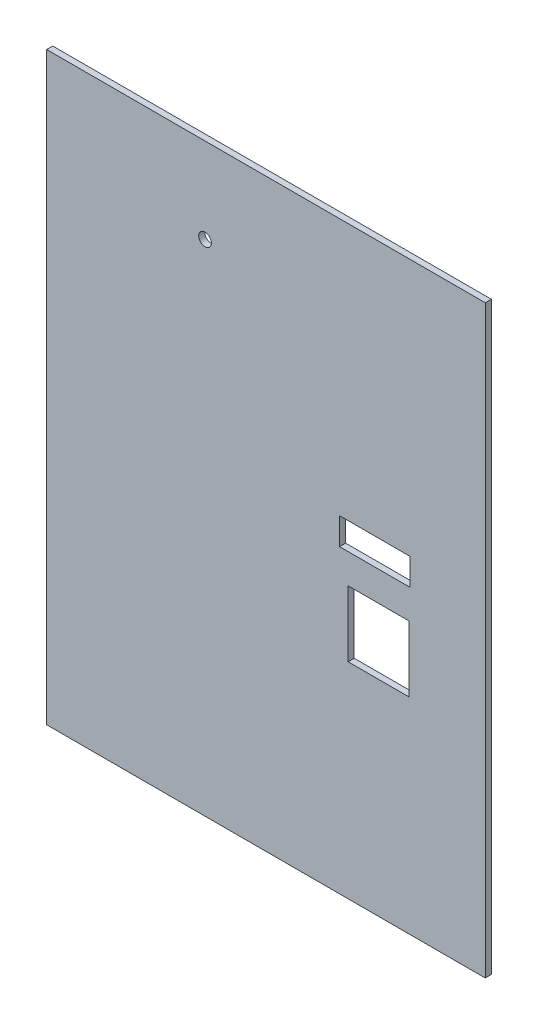
SolidWorks part; units mm, degrees
ref_plane "Front Plane" through (0, 0, 0) normal (0, 0, 1) x (1, 0, 0)
ref_plane "Top Plane" through (0, 0, 0) normal (0, 1, 0) x (1, 0, 0)
ref_plane "Right Plane" through (0, 0, 0) normal (1, 0, 0) x (0, 0, -1)
sketch "Sketch1" plane through (0, 0, 0) normal (0, 0, 1) x (1, 0, 0)
  line L1 (0, 0) -> (-457.2, 0)
  line L2 (0, 0) -> (0, 609.6)
  line L3 (0, 609.6) -> (-457.2, 609.6)
  line L4 (-457.2, 0) -> (-457.2, 609.6)
  dimension "D1" = 609.6
  dimension "D2" = 457.2
extrude "Boss-Extrude2" add sketch "Sketch1" along normal blind 6.35
sketch "Sketch2" plane through (0, 0, 6.35) normal (0, 0, 1) x (1, 0, 0)
  line L1 (-79.4256, 213.9976) -> (-142.9256, 213.9976)
  line L2 (-79.4256, 213.9976) -> (-79.4256, 282.5776)
  line L3 (-79.4256, 282.5776) -> (-142.9256, 282.5776)
  line L4 (-142.9256, 213.9976) -> (-142.9256, 282.5776)
extrude "Cut-Extrude1" cut sketch "Sketch2" against normal up to next contours L2 L1 L4 L3
sketch "Sketch3" plane through (0, 0, 6.35) normal (0, 0, 1) x (1, 0, 0)
  line L1 (-78.1936, 313.471) -> (-151.8536, 313.471)
  line L2 (-78.1936, 313.471) -> (-78.1936, 341.411)
  line L3 (-78.1936, 341.411) -> (-151.8536, 341.411)
  line L4 (-151.8536, 313.471) -> (-151.8536, 341.411)
extrude "Cut-Extrude2" cut sketch "Sketch3" against normal blind 63.5 contours L2 L1 L4 L3
sketch "Sketch4" plane through (0, 0, 6.35) normal (0, 0, 1) x (1, 0, 0)
  line L0 (-313.7465, 609.6) -> (-313.7465, 520.7) construction
  line L1 (0, 609.6) -> (-457.2, 609.6) construction
  line L2 (-457.2, 520.7) -> (-292.1, 520.7) construction
  line L3 (-457.2, 609.6) -> (-457.2, 0) construction
  circle A0 centre (-292.1, 520.7) radius 6.604
  dimension "D1" = 13.208
extrude "Cut-Extrude3" cut sketch "Sketch4" against normal blind 6.35
